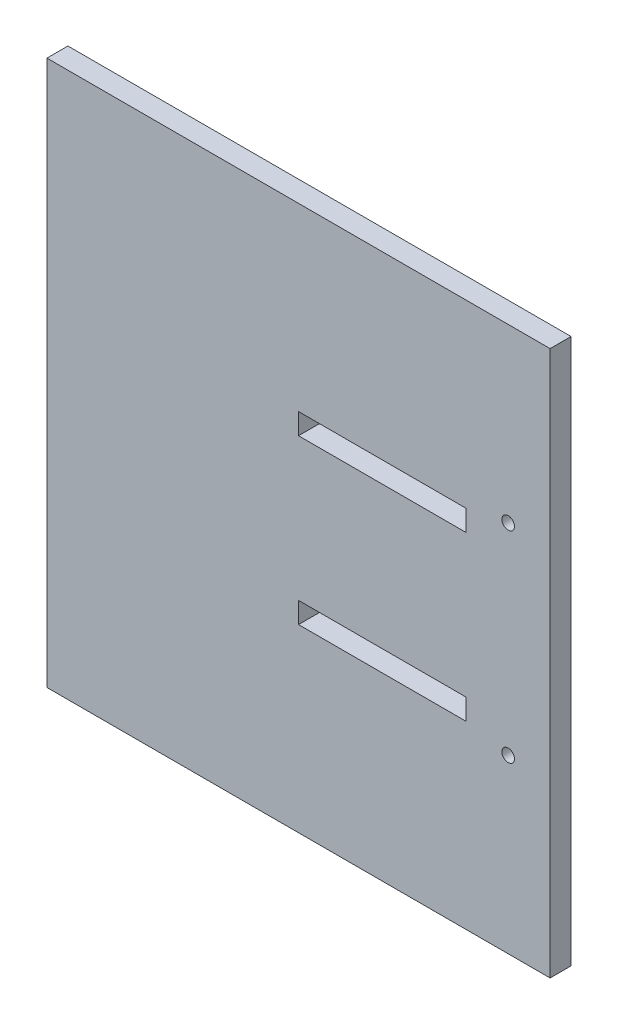
SolidWorks part; units mm, degrees
ref_plane "Front" through (0, 0, 0) normal (0, 0, 1) x (1, 0, 0)
ref_plane "Top" through (0, 0, 0) normal (0, 1, 0) x (1, 0, 0)
ref_plane "Right" through (0, 0, 0) normal (1, 0, 0) x (0, 0, -1)
sketch "Sketch2" plane through (0, 0, 0) normal (0, 0, 1) x (1, 0, 0)
  line L1 (-60, 65) -> (60, 65)
  line L2 (-60, 65) -> (-60, -65)
  line L3 (-60, -65) -> (60, -65)
  line L4 (60, 65) -> (60, -65)
  line L5 (-60, 65) -> (60, -65) construction
  line L6 (-60, -65) -> (60, 65) construction
  point P0 (0, 0)
  dimension "D1" = 130
  dimension "D2" = 120
extrude "Boss-Extrude1" add sketch "Sketch2" along normal blind 5
sketch "Sketch3" plane through (0, 0, 0) normal (0, 0, 1) x (1, 0, 0)
  line L0 (60, 0) -> (-60, 0) construction
  line L1 (40, 22) -> (0, 22)
  line L2 (40, 22) -> (40, 17)
  line L3 (40, 17) -> (0, 17)
  line L4 (0, 22) -> (0, 17)
  line L5 (40, 22) -> (0, 17) construction
  line L6 (40, 17) -> (0, 22) construction
  line L7 (60, -65) -> (60, 65) construction
  line L8 (50, 0) -> (-50, 0) construction
  line L9 (40, -17) -> (0, -17)
  line L10 (0, -22) -> (0, -17)
  line L11 (40, -22) -> (0, -22)
  line L12 (40, -22) -> (40, -17)
  line L13 (60, -65) -> (60, 65) construction
  line L14 (-60, 65) -> (-60, -65) construction
  circle A0 centre (50, 24) radius 1.5
  circle A1 centre (50, -24) radius 1.5
  point P0 (20, 19.5)
  dimension "D5" = 3
  dimension "D1" = 40
  dimension "D2" = 5
  dimension "D3" = 20
  dimension "D4" = 34
  dimension "D6" = 10
  dimension "D7" = 48
extrude "Cut-Extrude1" cut sketch "Sketch3" along normal through all
ref_plane "Plane1" through (60, 0, 0) normal (1, 0, 0) x (0, 0, -1)
sketch "Sketch4" plane through (60, 0, 0) normal (1, 0, 0) x (0, 0, -1)
  line L0 (0, 0) -> (-5, 0) construction
  line L1 (-5, -65) -> (-5, 65) construction
